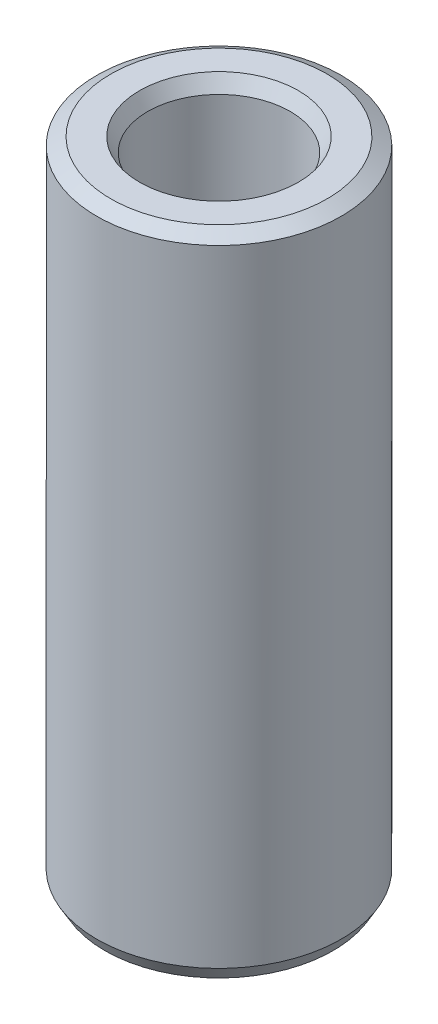
SolidWorks part; units mm, degrees
ref_plane "Front Plane" through (0, 0, 0) normal (0, 0, 1) x (1, 0, 0)
ref_plane "Top Plane" through (0, 0, 0) normal (0, 1, 0) x (1, 0, 0)
ref_plane "Right Plane" through (0, 0, 0) normal (1, 0, 0) x (0, 0, -1)
sketch "Sketch1" plane through (0, 0, 0) normal (0, 1, 0) x (1, 0, 0)
  circle A0 centre (0, 0) radius 42.5
  dimension "SLEEVE_OD" = 85
extrude "Boss-Extrude1" add sketch "Sketch1" along normal blind 225.431
sketch "Sketch2" plane through (0, 0, 0) normal (0, 1, 0) x (1, 0, 0)
  circle A0 centre (0, 0) radius 24.8002
  dimension "BORE_D" = 49.6005
extrude "Cut-Extrude1" cut sketch "Sketch2" along normal through all
chamfer "Chamfer1" distance 2.8161 angle 60 4 edges at (0, 225.431, 24.8002) (0, 0, 24.8002) (0, 0, 42.5) (0, 225.431, 42.5) first distance on face at (0, 225.431, 24.8002) first distance on face at (0, 0, 24.8002) first distance on face at (0, 225.431, 42.5)
